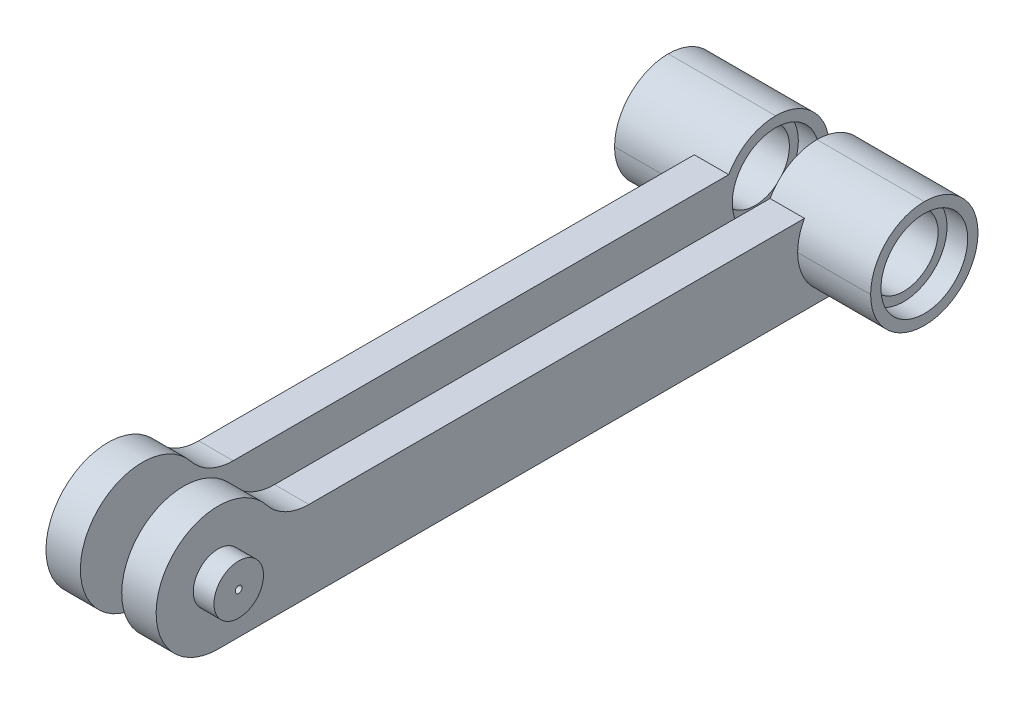
SolidWorks part; units mm, degrees
ref_plane "前视基准面" through (0, 0, 0) normal (0, 0, 1) x (1, 0, 0)
ref_plane "上视基准面" through (0, 0, 0) normal (0, 1, 0) x (1, 0, 0)
ref_plane "右视基准面" through (0, 0, 0) normal (1, 0, 0) x (0, 0, -1)
other "Configuration Table"
sketch "草图1" plane through (0, 0, 0) normal (1, 0, 0) x (0, 0, -1)
  line L0 (46, 3.3) -> (46, -4.5) construction
  line L1 (0, -4.5) -> (49.9, -4.5)
  line L2 (0, -4.5) -> (0, 3.3)
  line L3 (0, 3.3) -> (49.9, 3.3)
  line L4 (49.9, -4.5) -> (49.9, 3.3)
  line L6 (42.1, -4.5) -> (49.9, -4.5)
  line L7 (42.1, -4.5) -> (42.1, 3.3)
  line L8 (42.1, 3.3) -> (49.9, 3.3)
  line L9 (49.9, -4.5) -> (49.9, 3.3)
  line L10 (42.1, -4.5) -> (49.9, 3.3) construction
  line L11 (42.1, 3.3) -> (49.9, -4.5) construction
  circle A4 centre (0, 0) radius 1.8
  circle A5 centre (0, 0) radius 4.5
  circle A6 centre (46, -0.6) radius 2.5
  circle A7 centre (46, -0.6) radius 3.15
  circle A8 centre (0, 0) radius 0.25
  point P9 (46, -0.6)
  dimension "D1" = 3.6
  dimension "D4" = 46
  dimension "D5" = 3.9
  dimension "D2" = 9
  dimension "D6" = 5
  dimension "D7" = 6.3
  dimension "D8" = 0.5
  dimension "D3" = 7.8
extrude "凸台-拉伸1" add sketch "草图1" along normal blind 2.5 contours A5 | L3 L4 L1 L2
extrude "凸台-拉伸3" add sketch "草图1<6>" along normal blind 1.5 from surface contours L2 A4 | L2 A4 region at (0, 0, 0.7769) region at (0, 0, -0.7769) starting at face at (2.5, -0.0392, -24.2851)
sketch "草图1<6>" plane through (0, 0, 0) normal (1, 0, 0) x (0, 0, -1) same geometry as "草图1"
extrude "凸台-拉伸2" add sketch "草图1<5>" along normal blind 7.8 contours A6 | A7 A6 | L7 L1 L4 L3 A7 region at (0, -0.6, -42.2103) region at (0, -0.6, -46) region at (0, -0.6, -42.9391)
sketch "草图1<5>" plane through (0, 0, 0) normal (1, 0, 0) x (0, 0, -1) same geometry as "草图1"
extrude "切除-拉伸1" cut sketch "草图1<7>" along normal through all contours A6 region at (0, -0.6, -46)
sketch "草图1<7>" plane through (0, 0, 0) normal (1, 0, 0) x (0, 0, -1) same geometry as "草图1"
extrude "切除-拉伸2" cut sketch "草图1<8>" along normal blind 1.5 contours A7 A6 region at (0, -0.6, -42.9391)
sketch "草图1<8>" plane through (0, 0, 0) normal (1, 0, 0) x (0, 0, -1) same geometry as "草图1"
extrude "切除-拉伸3" cut sketch "草图1<9>" against normal blind 1.5 from surface contours A7 A6 region at (0, -0.6, -42.9391) starting at face at (7.8, -0.6, -48.5)
sketch "草图1<9>" plane through (0, 0, 0) normal (1, 0, 0) x (0, 0, -1) same geometry as "草图1"
sketch "草图2" plane through (0, 0, 0) normal (-1, 0, 0) x (0, 0, 1)
  line L0 (-3.0594, 3.3) -> (-49.9, 3.3) construction
  line L1 (-42.1, 3.3) -> (-4.5, 3.3)
  line L2 (-42.1, 3.3) -> (-42.1, 1.3)
  line L3 (-42.1, 1.3) -> (-4.5, 1.3)
  line L4 (-4.5, 3.3) -> (-4.5, 1.3)
  line L5 (-42.1, 3.3) -> (-42.1, -4.5) construction
  line L6 (-4.5, 3.3) -> (-3.0594, 3.3)
  line L8 (-4.5, 1.3) -> (-4.3081, 1.3)
  line L9 (-4.5, 1.3) -> (-4.5, 3.3)
  line L10 (-4.5, 3.3) -> (-4.3081, 3.3)
  line L11 (-4.3081, 1.3) -> (-4.3081, 3.3)
  arc A1 (0, -4.5) -> (-3.0594, 3.3) centre (0, 0) ccw construction
  circle A2 centre (0, 0) radius 4.5
  line M7 (-3.0594, 3.3) -> (-49.9, 3.3)
  dimension "D1" = 2
extrude "切除-拉伸4" cut sketch "草图2" against normal through all contours A2 L11 M7 | L8 L11 L6 L4 | L4 L2 L3 M7 region at (0, 2.3, -23.3) region at (0, 2.3, -4.4041) region at (0, 2.7076, -3.9302)
fillet "圆角1" radius 3.9 5 edges at (3.9, -4.5, -49.9) (3.9, 3.3, -49.9) (5.15, -4.5, -42.1) (3.9, 3.3, -42.1) (1.25, 1.3, -4.3081)
ref_plane "基准面1" through (-1.5, 0, 0) normal (1, 0, 0) x (0, 0, -1)
mirror "镜向1" about plane through (-1.5, 0, 0) normal (1, 0, 0) of bodies 118
